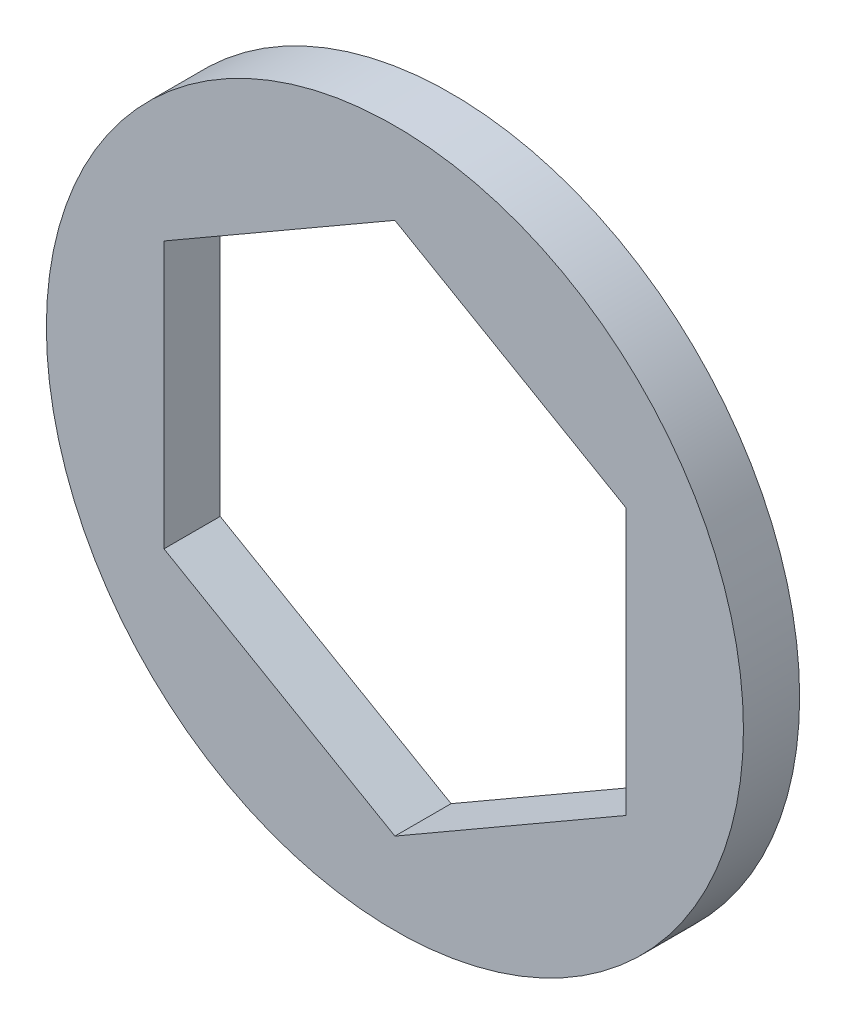
SolidWorks part; units mm, degrees
material "Nylon 101"
ref_plane "Front Plane" through (0, 0, 0) normal (0, 0, 1) x (1, 0, 0)
ref_plane "Top Plane" through (0, 0, 0) normal (0, 1, 0) x (1, 0, 0)
ref_plane "Right Plane" through (0, 0, 0) normal (1, 0, 0) x (0, 0, -1)
sketch "Sketch1" plane through (0, 0, 0) normal (0, 0, 1) x (1, 0, 0)
  line L1 (0, 7.7723) -> (-6.731, 3.8861)
  line L2 (-6.731, 3.8861) -> (-6.731, -3.8861)
  line L3 (-6.731, -3.8861) -> (0, -7.7723)
  line L4 (0, -7.7723) -> (6.731, -3.8861)
  line L5 (6.731, -3.8861) -> (6.731, 3.8861)
  line L6 (6.731, 3.8861) -> (0, 7.7723)
  circle A0 centre (0, 0) radius 10.16
  circle A1 centre (0, 0) radius 6.731 construction
  dimension "D1" = 13.462
  dimension "D2" = 20.32
extrude "Boss-Extrude1" add sketch "Sketch1" along normal mid plane 1.6383
